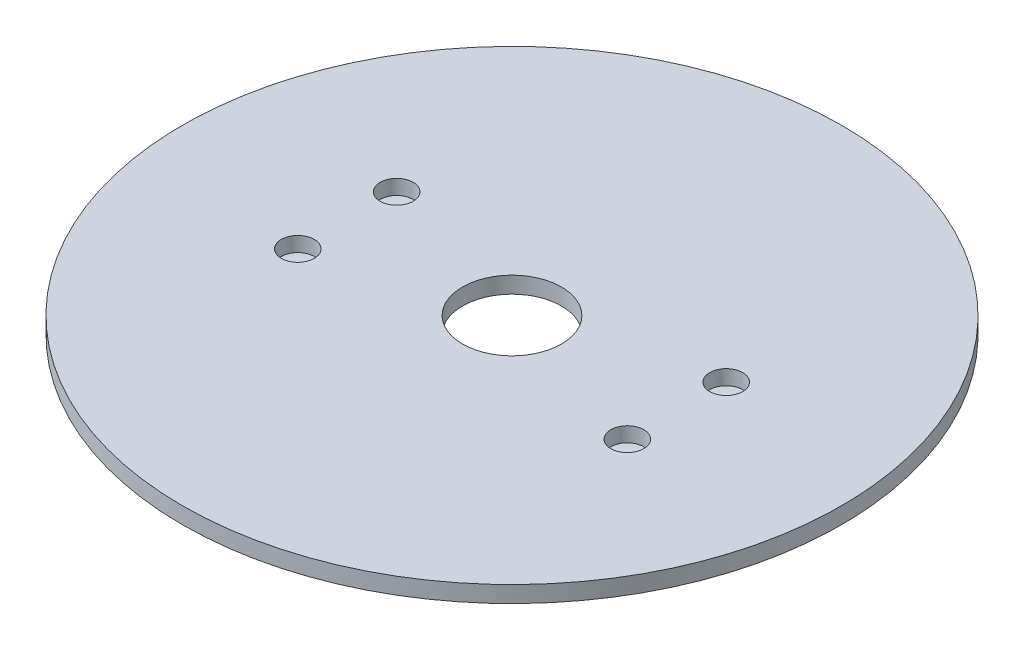
SolidWorks part; units mm, degrees
ref_plane "Front Plane" through (0, 0, 0) normal (0, 0, 1) x (1, 0, 0)
ref_plane "Top Plane" through (0, 0, 0) normal (0, 1, 0) x (1, 0, 0)
ref_plane "Right Plane" through (0, 0, 0) normal (1, 0, 0) x (0, 0, -1)
sketch "Sketch1" plane through (0, 0, 0) normal (0, 1, 0) x (1, 0, 0)
  circle A0 centre (0, 0) radius 1000
  dimension "D1" = 2000
extrude "Boss-Extrude1" add sketch "Sketch1" along normal blind 50
sketch "Sketch2" plane through (0, 50, 0) normal (0, 1, 0) x (1, 0, 0)
  line L0 (0, 0) -> (1000, 0)
  line L1 (500, 0) -> (500, 150)
  line L2 (500, 0) -> (500, -150)
  circle A0 centre (0, 0) radius 1000 construction
  circle A1 centre (500, 150) radius 50
  circle A2 centre (500, -150) radius 50
  dimension "D1" = 150
  dimension "D2" = 150
extrude "Cut-Extrude2" cut sketch "Sketch2" against normal blind 45 contours A1
extrude "Cut-Extrude3" cut sketch "Sketch2<4>" against normal blind 45 contours A2 region at (534.3553, 50, 115.6447)
sketch "Sketch2<4>" plane through (0, 50, 0) normal (0, 1, 0) x (1, 0, 0) same geometry as "Sketch2"
sketch "Sketch3" plane through (0, 50, 0) normal (0, 1, 0) x (1, 0, 0)
  line L0 (0, 0) -> (-1000, 0)
  line L2 (-500, 0) -> (-500, 150)
  line L3 (-500, 0) -> (-500, -150)
  circle A0 centre (0, 0) radius 1000 construction
  circle A2 centre (-500, 150) radius 50
  circle A3 centre (-500, -150) radius 50
  dimension "D1" = 150
  dimension "D2" = 150
extrude "Cut-Extrude4" cut sketch "Sketch3" against normal blind 45 contours A2 | A3 region at (-534.3553, 50, -184.3553) region at (-465.6447, 50, 115.6447)
sketch "Sketch4" plane through (0, 50, 0) normal (0, 1, 0) x (1, 0, 0)
  circle A0 centre (0, 0) radius 150
extrude "Cut-Extrude5" cut sketch "Sketch4" against normal blind 50
